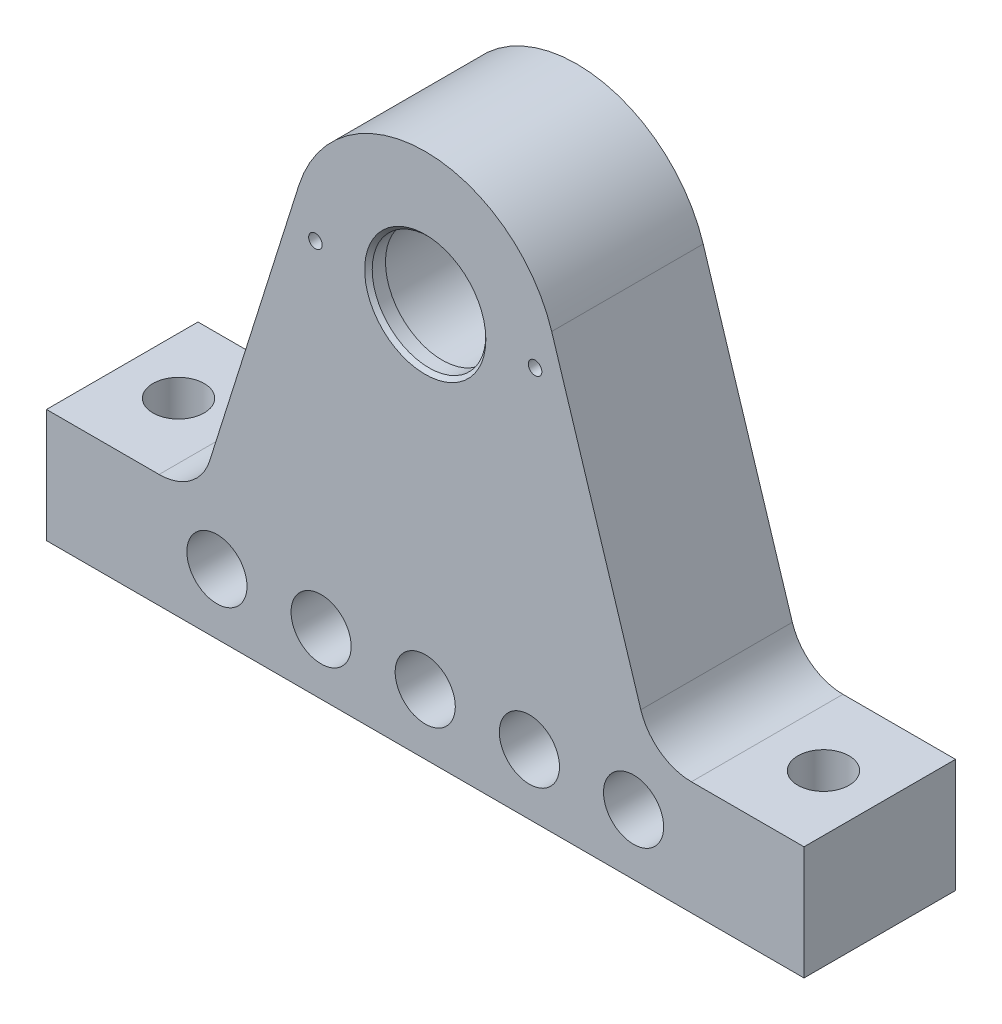
SolidWorks part; units mm, degrees
material "AISI 316 Annealed Stainless Steel Bar (SS)"
ref_plane "Front" through (0, 0, 0) normal (0, 0, 1) x (1, 0, 0)
ref_plane "Top" through (0, 0, 0) normal (0, 1, 0) x (1, 0, 0)
ref_plane "Right" through (0, 0, 0) normal (1, 0, 0) x (0, 0, -1)
sketch "Sketch1" plane through (0, 0, 0) normal (0, 0, 1) x (1, 0, 0)
  line L0 (-50, 0) -> (50, 0)
  line L1 (50, 0) -> (50, 15)
  line L3 (-50, 15) -> (-50, 0)
  line L4 (0, 0) -> (0, 52) construction
  line L5 (0, 52) -> (16.6918, 57.2568) construction
  line L6 (0, 52) -> (-16.6918, 57.2568) construction
  line L7 (50, 15) -> (30, 15)
  line L8 (-50, 15) -> (-30, 15)
  line L11 (-16.6918, 57.2568) -> (-30, 15)
  line L12 (16.6918, 57.2568) -> (30, 15)
  arc A0 (16.6918, 57.2568) -> (-16.6918, 57.2568) centre (0, 52) ccw
  circle A3 centre (0, 52) radius 4.7625 construction
  dimension "D3" = 17.5
  dimension "D6" = 9.525
  dimension "D1" = 100
  dimension "D2" = 52
  dimension "D4" = 15
  dimension "D5" = 20
extrude "Boss-Extrude1" add sketch "Sketch1" along normal blind 20
fillet "Fillet1" radius 7 2 edges at (30, 15, 10) (-30, 15, 10)
hole_wizard "CBORE for #8 Socket Head Cap Screw1" positions "Sketch2" profile "Sketch3" counterbore size "#8" standard "ANSI Inch" end condition through all
sketch "Sketch2" plane through (0, 0, 20) normal (0, 0, 1) x (1, 0, 0)
  line L0 (0, 0) -> (0, 8)
  line L1 (-50, 0) -> (50, 0) construction
  line L3 (-27.5, 8) -> (0, 8)
  line L5 (0, 8) -> (27.5, 8)
  point P0 (0, 8)
  point P21 (-27.5, 8)
  point P22 (-13.75, 8)
  point P24 (13.75, 8)
  point P28 (27.5, 8)
  dimension "D1" = 8
  dimension "D2" = 27.5
sketch "Sketch3" plane through (0, 8, 20) normal (1, 0, 0) x (0, -1, 0)
  line L0 (0, 0) -> (0, 20)
  line L1 (0, 20) -> (2.2479, 20)
  line L3 (2.2479, 20) -> (2.2479, 10)
  line L4 (2.2479, 10) -> (3.9687, 10)
  line L5 (3.9687, 10) -> (3.9687, 0)
  line L7 (3.9687, 0) -> (0, 0)
  line L11 (0, -6.35) -> (0, 107.95) construction
  dimension "Thru Hole Dia." = 4.4958
  dimension "Thru Hole Depth" = 20
  dimension "C'Bore Dia." = 7.9375
  dimension "C'Bore Depth" = 10
sketch "Sketch4" plane through (0, 0, 0) normal (1, 0, 0) x (0, 0, -1)
  line L0 (0, 52) -> (-20, 52)
  line L1 (-20, 52) -> (-20, 44.5)
  line L2 (-20, 44.5) -> (-17.75, 44.5)
  line L3 (-17.75, 44.5) -> (-17.75, 44)
  line L4 (-17.75, 44) -> (-7, 44)
  line L5 (-7, 44) -> (-7, 41)
  line L6 (-7, 41) -> (0, 41)
  line L7 (0, 0) -> (0, 52) construction
  line L8 (0, 41) -> (0, 52)
  point P3 (-10, 52)
  dimension "D1" = 11
  dimension "D2" = 8
  dimension "D3" = 7.5
  dimension "D4" = 2.25
  dimension "D5" = 7
revolve "Cut-Revolve1" cut sketch "Sketch4" angle 360 about L0
hole_wizard "#2-56 Tapped Hole1" positions "Sketch5" profile "Sketch6" tap size "#2-56" standard "ANSI Inch"
sketch "Sketch5" plane through (0, 0, 20) normal (0, 0, 1) x (1, 0, 0)
  line L0 (14.5, 52) -> (-14.5, 52) construction
  line L3 (0, 0) -> (0, 52) construction
  line L4 (-50, 0) -> (50, 0) construction
  circle A1 centre (0, 52) radius 7.5 construction
  point P0 (14.5, 52)
  point P2 (-14.5, 52)
  dimension "D1" = 29
sketch "Sketch6" plane through (14.5, 52, 20) normal (1, 0, 0) x (0, -1, 0)
  line L0 (0, 0) -> (0, 6.2642)
  line L1 (0, 6.2642) -> (0.889, 5.73)
  line L2 (0.889, 5.73) -> (0.889, 0)
  line L5 (0.889, 0) -> (0, 0)
  line L10 (0, 6.2642) -> (-0.889, 5.73) construction
  line L11 (0, -6.35) -> (0, 107.95) construction
  dimension "Tap Drill Dia." = 1.778
  dimension "Tap Drill Depth" = 5.73
  dimension "Drill Angle" = 118
cosmetic thread "Hole Thread1" parameters "D1"=4.37, "D2"=2.1844
cosmetic thread "Hole Thread2" parameters "D1"=4.37, "D2"=2.1844
chamfer "Chamfer1" distance 0.5 angle 45 2 edges at (-7.5, 52, 20) (-11, 52, 0)
hole_wizard "1/8 (0.1250) Dowel Hole1" positions "Sketch9" profile "Sketch10" hole size "1/8" standard "ANSI Inch"
sketch "Sketch9" plane through (0, 0, 0) normal (0, 0, -1) x (-1, 0, 0)
  line L0 (27.5, 8) -> (13.75, 8) construction
  point P0 (20.625, 8)
sketch "Sketch10" plane through (-20.625, 8, 0) normal (1, 0, 0) x (0, 1, 0)
  line L0 (0, 0) -> (0, 6.9539)
  line L1 (0, 6.9539) -> (1.5875, 6)
  line L2 (1.5875, 6) -> (1.5875, 0)
  line L5 (1.5875, 0) -> (0, 0)
  line L10 (0, 6.9539) -> (-1.5875, 6) construction
  line L11 (0, -6.35) -> (0, 107.95) construction
  dimension "Hole Dia." = 3.175
  dimension "Hole Depth" = 6
  dimension "Drill Angle" = 118
hole_wizard "1/8 (0.1250) Dowel Slot1" positions "Sketch11" profile "Sketch12" size "1/8" standard "ANSI Inch" slot yes
sketch "Sketch11" plane through (0, 0, 0) normal (0, 0, -1) x (-1, 0, 0)
  line L0 (-18.625, 8) -> (-22.625, 8) construction
  line L1 (-13.75, 8) -> (-27.5, 8) construction
  point P0 (-20.625, 8)
  dimension "D1" = 4
sketch "Sketch12" plane through (20.625, 8, 0) normal (1, 0, 0) x (0, 1, 0)
  line L0 (0, 0) -> (0, 6.9539)
  line L1 (0, 6.9539) -> (1.5875, 6)
  line L2 (1.5875, 6) -> (1.5875, 0)
  line L5 (1.5875, 0) -> (0, 0)
  line L10 (0, 6.9539) -> (-1.5875, 6) construction
  line L11 (0, -6.35) -> (0, 107.95) construction
  dimension "Hole Dia." = 3.175
  dimension "Hole Depth" = 6
  dimension "Drill Angle" = 118
sketch "Sketch13" plane through (0, 0, 0) normal (0, 0, -1) x (-1, 0, 0)
  circle A0 centre (0, 52) radius 10
  dimension "D1" = 20
extrude "Cut-Extrude1" [suppressed] cut sketch "Sketch13" along normal blind 1.1 from offset 2 offset against normal yes
hole_wizard "1/4 Clearance Hole1" positions "Sketch16" profile "Sketch17" hole size "1/4" standard "ANSI Inch" end condition through all
sketch "Sketch16" plane through (0, 15, 0) normal (0, 1, 0) x (1, 0, 0)
  line L0 (50, -10) -> (35.1344, -10) construction
  line L1 (50, -20) -> (50, 0) construction
  line L4 (-35.1344, -10) -> (-50, -10) construction
  line L6 (-50, -20) -> (-50, 0) construction
  line L7 (-35.1344, -20) -> (-35.1344, 0) construction
  line L8 (35.1344, 0) -> (35.1344, -20) construction
  point P0 (42.5672, -10)
  point P2 (-42.5672, -10)
sketch "Sketch17" plane through (42.5672, 15, 10) normal (1, 0, 0) x (0, 0, 1)
  line L0 (0, 0) -> (0, 15)
  line L1 (0, 15) -> (3.3782, 15)
  line L2 (3.3782, 15) -> (3.3782, 0)
  line L5 (3.3782, 0) -> (0, 0)
  line L11 (0, -6.35) -> (0, 107.95) construction
  dimension "Thru Hole Dia." = 6.7564
  dimension "Thru Hole Depth" = 15
